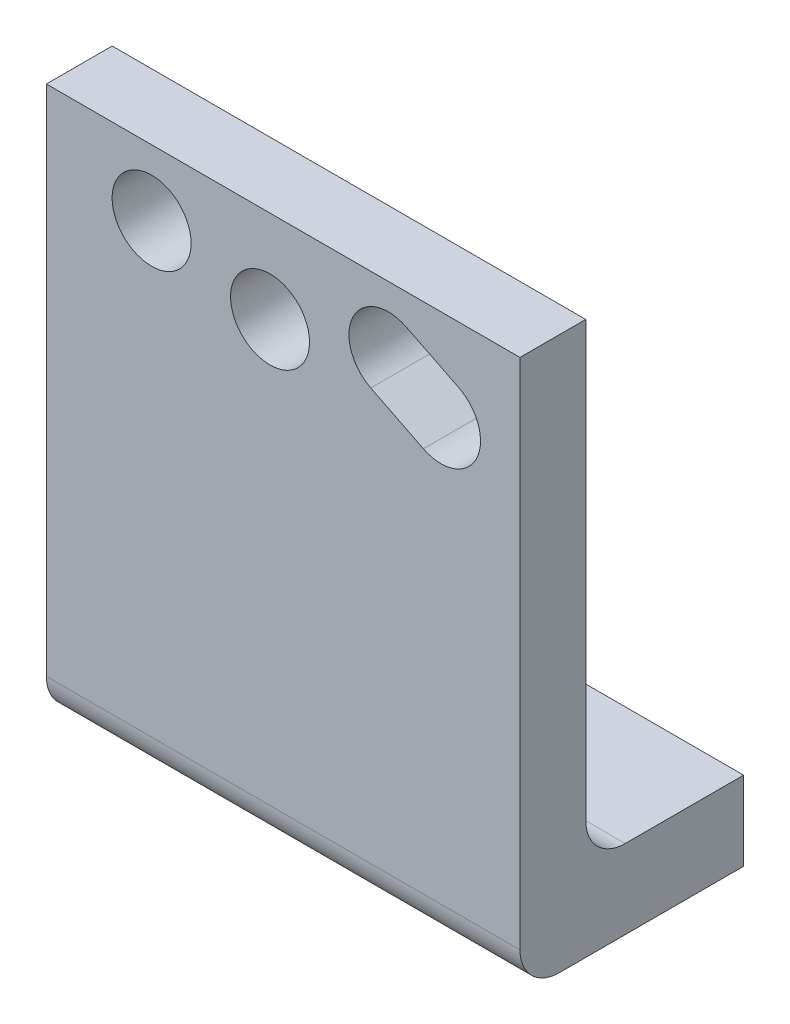
SolidWorks part; units mm, degrees
ref_plane "Front Plane" through (0, 0, 0) normal (0, 0, 1) x (1, 0, 0)
ref_plane "Top Plane" through (0, 0, 0) normal (0, 1, 0) x (1, 0, 0)
ref_plane "Right Plane" through (0, 0, 0) normal (1, 0, 0) x (0, 0, -1)
sketch "Sketch1" plane through (0, 0, 0) normal (0, 0, 1) x (1, 0, 0)
  line L0 (-9, 8) -> (9, 8) construction
  line L1 (-9, 10.5) -> (9, 10.5)
  line L2 (-9, 10.5) -> (-9, -10.5)
  line L3 (-9, -10.5) -> (9, -10.5)
  line L4 (9, 10.5) -> (9, -10.5)
  line L5 (-9, 10.5) -> (9, -10.5) construction
  line L6 (-9, -10.5) -> (9, 10.5) construction
  line L7 (-9, 3.5) -> (9, 3.5) construction
  line L8 (-9, -10.5) -> (9, -10.5)
  line L9 (-9, -10.5) -> (-9, -7.5)
  line L10 (-9, -7.5) -> (9, -7.5)
  line L11 (9, -10.5) -> (9, -7.5)
  line L12 (-9, 7) -> (9, 7) construction
  line L13 (4.6708, 9.3416) -> (6.6708, 8.3416)
  line L14 (5.3292, 5.6584) -> (3.3292, 6.6584)
  circle A0 centre (-5, 8) radius 1.5
  circle A1 centre (4, 8) radius 1.5
  circle A2 centre (6, 7) radius 1.5
  circle A3 centre (-0.5, 7) radius 1.5
  point P0 (0, 0)
  dimension "D11" = 3
  dimension "D1" = 11
  dimension "D2" = 3
  dimension "D3" = 18
  dimension "D4" = 7
  dimension "D5" = 4.5
  dimension "D6" = 3.5
  dimension "D7" = 6.5
  dimension "D8" = 9
  dimension "D9" = 4
  dimension "D10" = 3
  dimension "D12" = 3.5
extrude "Boss-Extrude1" add sketch "Sketch1" along normal blind 2.5 contours L2 L10 L4 L1 A3 A2 L14 A1 L13 A0 | L10 L2 L3 L4 region at (-0.1013, 0.9343, 0) region at (0, -9, 0)
extrude "Boss-Extrude2" add sketch "Sketch1<3>" against normal blind 6 contours L10 L2 L3 L4 region at (0, -9, 0)
sketch "Sketch1<3>" plane through (0, 0, 0) normal (0, 0, 1) x (1, 0, 0) same geometry as "Sketch1"
fillet "Fillet1" radius 1.5 2 edges at (0, -10.5, 2.5) (0, -7.5, 0)
